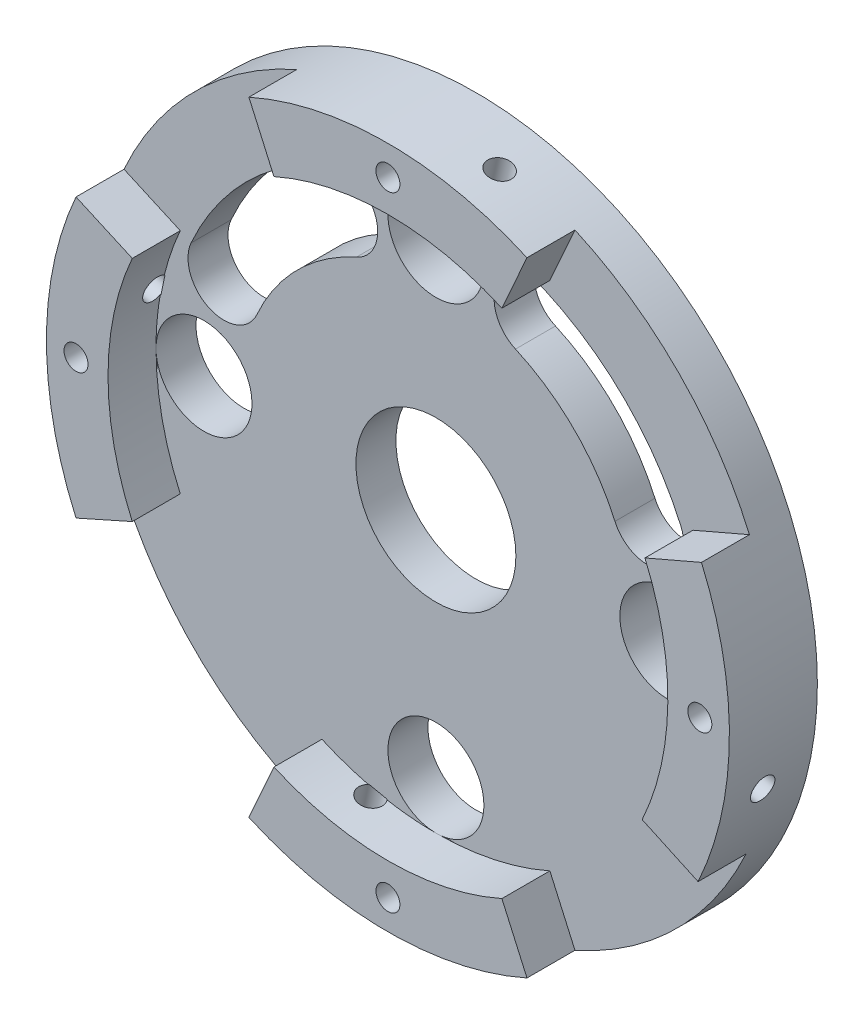
SolidWorks part; units mm, degrees
ref_plane "前视基准面" through (0, 0, 0) normal (0, 0, 1) x (1, 0, 0)
ref_plane "上视基准面" through (0, 0, 0) normal (0, 1, 0) x (1, 0, 0)
ref_plane "右视基准面" through (0, 0, 0) normal (1, 0, 0) x (0, 0, -1)
sketch "草图1" plane through (0, 0, 0) normal (0, 0, 1) x (1, 0, 0)
  circle A0 centre (0, 0) radius 42.7
extrude "凸台-拉伸1" add sketch "草图1" along normal blind 5
sketch "草图2" plane through (0, 0, 5) normal (0, 0, 1) x (1, 0, 0)
  circle A0 centre (0, 0) radius 42.7
  circle A1 centre (0, 0) radius 35
extrude "凸台-拉伸2" add sketch "草图2" along normal blind 6
sketch "草图3" plane through (0, 0, 11) normal (0, 0, 1) x (1, 0, 0)
  line L0 (0, 42.7) -> (0, 39)
  line L1 (42.7, 0) -> (39, 0)
  line L2 (0, -42.7) -> (0, -39)
  line L3 (-42.7, 0) -> (-39, 0)
  circle A0 centre (0, 0) radius 42.7 construction
  circle A1 centre (0, 39) radius 1.5
  circle A2 centre (39, 0) radius 1.5
  circle A3 centre (0, -39) radius 1.5
  circle A4 centre (-39, 0) radius 1.5
extrude "切除-拉伸1" cut sketch "草图3" against normal blind 11 contours A1 | A2 | A3 | A4 region at (-1.0307, 37.9693, 11) region at (37.5424, 0, 11) region at (1.0307, -40.0307, 11) region at (-39, -1.4576, 11)
sketch "草图4" plane through (0, 0, 11) normal (0, 0, 1) x (1, 0, 0)
  circle A0 centre (0, 0) radius 29
  circle A1 centre (0, 29) radius 6
  circle A2 centre (-29, 0) radius 6
  circle A3 centre (0, -29) radius 6
  circle A4 centre (29, 0) radius 6
extrude "切除-拉伸2" cut sketch "草图4" against normal blind 11 contours A1 A0 | A0 A1 | A0 A4 | A4 A0 | A0 A3 | A0 A3 | A0 A2 | A0 A2 region at (26.345, 0, 11) region at (31.4314, 0, 11) region at (0, 26.345, 11) region at (0, 31.4314, 11) region at (0, -31.4314, 11) region at (0, -26.345, 11) region at (-26.345, 0, 11) region at (-31.4314, 0, 11)
sketch "草图5" plane through (0, 0, 5) normal (0, 0, 1) x (1, 0, 0)
  line L0 (0, 26.5) -> (0, 29)
  line L1 (0, 26.5) -> (11.7792, 26.5)
  line L2 (11.7792, 26.5) -> (-11.7792, 26.5)
  line L3 (-26.5, 0) -> (-29, 0)
  line L4 (-26.5, 0) -> (-26.5, 11.7792)
  line L5 (-26.5, 11.7792) -> (-26.5, -11.7792)
  line L6 (26.5, 0) -> (29, 0)
  line L7 (0, -26.5) -> (11.7792, -26.5)
  line L8 (11.7792, -26.5) -> (-11.7792, -26.5)
  line L9 (0, -26.5) -> (0, -29)
  line L10 (26.5, 0) -> (26.5, -11.7792)
  line L11 (26.5, -11.7792) -> (26.5, 11.7792)
  arc A0 (26.5, 11.7792) -> (11.7792, 26.5) centre (0, 0) ccw construction
  arc A1 (30.6121, 13.607) -> (13.607, 30.6121) centre (0, 0) ccw
  arc A2 (22.3879, 9.9514) -> (9.9514, 22.3879) centre (0, 0) ccw
  arc A3 (22.3879, 9.9514) -> (30.6121, 13.607) centre (26.5, 11.7792) ccw
  arc A4 (13.607, 30.6121) -> (9.9514, 22.3879) centre (11.7792, 26.5) ccw
  circle A5 centre (0, 0) radius 29
  arc A6 (26.5, -11.7792) -> (11.7792, -26.5) centre (0, 0) cw construction
  arc A7 (13.607, -30.6121) -> (30.6121, -13.607) centre (0, 0) ccw
  arc A8 (9.9514, -22.3879) -> (22.3879, -9.9514) centre (0, 0) ccw
  arc A9 (9.9514, -22.3879) -> (13.607, -30.6121) centre (11.7792, -26.5) ccw
  arc A10 (30.6121, -13.607) -> (22.3879, -9.9514) centre (26.5, -11.7792) ccw
  arc A11 (-11.7792, -26.5) -> (-26.5, -11.7792) centre (0, 0) cw construction
  arc A12 (-30.6121, -13.607) -> (-13.607, -30.6121) centre (0, 0) ccw
  arc A13 (-22.3879, -9.9514) -> (-9.9514, -22.3879) centre (0, 0) ccw
  arc A14 (-22.3879, -9.9514) -> (-30.6121, -13.607) centre (-26.5, -11.7792) ccw
  arc A15 (-13.607, -30.6121) -> (-9.9514, -22.3879) centre (-11.7792, -26.5) ccw
  arc A16 (-26.5, 11.7792) -> (-11.7792, 26.5) centre (0, 0) cw construction
  arc A17 (-13.607, 30.6121) -> (-30.6121, 13.607) centre (0, 0) ccw
  arc A18 (-9.9514, 22.3879) -> (-22.3879, 9.9514) centre (0, 0) ccw
  arc A19 (-9.9514, 22.3879) -> (-13.607, 30.6121) centre (-11.7792, 26.5) ccw
  arc A20 (-30.6121, 13.607) -> (-22.3879, 9.9514) centre (-26.5, 11.7792) ccw
  point P17 (20.5061, 20.5061)
  point P23 (20.5061, -20.5061)
  point P35 (-20.5061, -20.5061)
  point P41 (-20.5061, 20.5061)
extrude "切除-拉伸3" cut sketch "草图5" against normal blind 11 contours L11 A5 L2 A4 A2 A3 | A5 A3 A1 A4 | A3 A5 L11 | L2 A5 A4 | A17 A20 A5 A19 | L5 A20 A18 A19 L2 A5 | L2 A19 A5 | A5 A20 L5 region at (8.8958, 27.0257, 5) region at (18.2527, 18.2527, 5) region at (-18.2527, 18.2527, 5) region at (-8.8958, 27.0257, 5) region at (21.2116, 21.2116, 5) region at (-21.2116, 21.2116, 5) region at (27.0257, 8.8958, 5) region at (-27.0257, 8.8958, 5)
sketch "草图6" plane through (0, 0, 5) normal (0, 0, 1) x (1, 0, 0)
  circle A0 centre (0, 0) radius 10
extrude "切除-拉伸4" cut sketch "草图6" against normal blind 11
sketch "草图7" plane through (0, 0, 11) normal (0, 0, 1) x (1, 0, 0)
  line L0 (0, 39) -> (17.3865, 39)
  line L1 (17.3865, 39) -> (-17.3865, 39)
  line L2 (-39, 0) -> (-39, 17.3865)
  line L3 (-39, 17.3865) -> (-39, -17.3865)
  line L4 (0, -39) -> (17.3865, -39)
  line L5 (17.3865, -39) -> (-17.3865, -39)
  line L6 (39, 0) -> (39.2065, 16.9156)
  line L7 (39.2065, 16.9156) -> (38.7818, -17.8678)
  line L8 (38.7818, -17.8678) -> (31.7884, -14.6458)
  line L9 (17.3865, -39) -> (14.2512, -31.9672)
  line L10 (-17.3865, -39) -> (-14.2512, -31.9672)
  line L11 (-39, -17.3865) -> (-31.9672, -14.2512)
  line L12 (-39, 17.3865) -> (-31.9672, 14.2512)
  line L13 (-17.3865, 39) -> (-14.2512, 31.9672)
  line L14 (17.3865, 39) -> (14.2512, 31.9672)
  line L15 (39.2065, 16.9156) -> (32.1365, 13.8652)
  circle A0 centre (0, 0) radius 35
  circle A1 centre (0, 0) radius 42.7
  circle M5 centre (0, 0) radius 42.7
  circle M6 centre (0, 0) radius 35
extrude "切除-拉伸5" cut sketch "草图7" against normal blind 6 contours L13 L12 M5 M6 | L15 L14 M5 M6 | L9 L8 M5 M6 | L11 L10 M5 M6 region at (27.0912, 26.7669, 11) region at (-26.9497, 26.9497, 11) region at (-26.9497, -26.9497, 11) region at (26.8026, -27.1364, 11)
sketch "草图8" plane through (0, 0, 0) normal (1, 0, 0) x (0, 0, -1)
  line L0 (-11.8111, 0) -> (0, 0)
ref_plane "基准面1" through (0, 0, 0) normal (0.9781, -0.2079, 0) x (0, 0, -1)
ref_plane "基准面2" through (0, 0, 0) normal (-0.2079, -0.9781, 0) x (0, 0, -1)
sketch "草图9" plane through (0, 0, 0) normal (-0.2079, -0.9781, 0) x (0, 0, -1)
  line L0 (-11.8111, 0) -> (0, 0) construction
  circle A0 centre (-5.9056, 0) radius 1.5
extrude "切除-拉伸6" cut sketch "草图9" against normal blind 50 and the other way blind 50 contours A0
sketch "草图10" plane through (0, 0, 0) normal (0.9781, -0.2079, 0) x (0, 0, -1)
  line L0 (-11.8111, 0) -> (0, 0) construction
  circle A0 centre (-5.9056, 0) radius 1.5
extrude "切除-拉伸7" cut sketch "草图10" against normal blind 50 and the other way blind 50 contours A0
sketch "草图11" plane through (0, 0, 5) normal (0, 0, 1) x (1, 0, 0)
  circle A0 centre (0, 0) radius 35
  circle A1 centre (0, 29) radius 6
  circle A2 centre (0, -29) radius 6
  circle A3 centre (-29, 0) radius 6
  circle A4 centre (29, 0) radius 6
  circle A5 centre (0, 0) radius 10
  circle A6 centre (0, 0) radius 29
sketch "草图13" plane through (0, 0, 0) normal (-0.2079, -0.9781, 0) x (0, 0, -1)
  line L0 (-11.8111, 0) -> (0, 0) construction
  line L1 (-5.9056, 1.5) -> (-5.9056, -1.5)
  circle A0 centre (-5.9056, 0) radius 1.5
extrude "凸台-拉伸12" add sketch "草图13" along normal blind 36 and the other way blind 36 contours A0
sketch "草图14" plane through (0, 0, 0) normal (0.9781, -0.2079, 0) x (0, 0, -1)
  line L0 (-11.8111, 0) -> (0, 0) construction
  circle A0 centre (-5.9056, 0) radius 1.5
extrude "凸台-拉伸13" add sketch "草图14" along normal blind 36 and the other way blind 36
sketch "草图15" plane through (0, 0, 11) normal (0, 0, 1) x (1, 0, 0)
  circle A0 centre (0, 0) radius 35
extrude "切除-拉伸8" cut sketch "草图15" against normal blind 6
sketch "草图16" plane through (0, 0, 5) normal (0, 0, 1) x (1, 0, 0)
  circle A0 centre (0, 0) radius 10
extrude "切除-拉伸9" cut sketch "草图16" against normal blind 6
sketch "草图17" plane through (35.2133, -7.4848, 0) normal (0.9781, -0.2079, 0) x (0, 0, -1)
  line L0 (-11.8111, 0) -> (0, 0) construction
  circle A0 centre (-5.9056, 0) radius 1.5
extrude "切除-拉伸11" cut sketch "草图17" against normal blind 1.1
sketch "草图18" plane through (-35.2133, 7.4848, 0) normal (-0.9781, 0.2079, 0) x (0, 0, 1)
  line L0 (11.8111, 0) -> (0, 0) construction
  circle A0 centre (5.9056, 0) radius 1.5
extrude "切除-拉伸12" cut sketch "草图18" against normal blind 1.1
sketch "草图19" plane through (7.4848, 35.2133, 0) normal (0.2079, 0.9781, 0) x (0.9781, -0.2079, 0)
  line L0 (0, -11.8111) -> (0, 0) construction
  circle A0 centre (0, -5.9056) radius 1.5
extrude "切除-拉伸13" cut sketch "草图19" against normal blind 1.1
sketch "草图20" plane through (-7.4848, -35.2133, 0) normal (-0.2079, -0.9781, 0) x (0.9781, -0.2079, 0)
  line L0 (0, 11.8111) -> (0, 0) construction
  circle A0 centre (0, 5.9056) radius 1.5
extrude "切除-拉伸14" cut sketch "草图20" against normal blind 1.1
sketch "草图21" plane through (0, 0, 5) normal (0, 0, 1) x (1, 0, 0)
  circle A0 centre (0, 29) radius 6
  circle A1 centre (-29, 0) radius 6
  circle A2 centre (0, -29) radius 6
  circle A3 centre (29, 0) radius 6
extrude "切除-拉伸15" cut sketch "草图21" against normal blind 5
